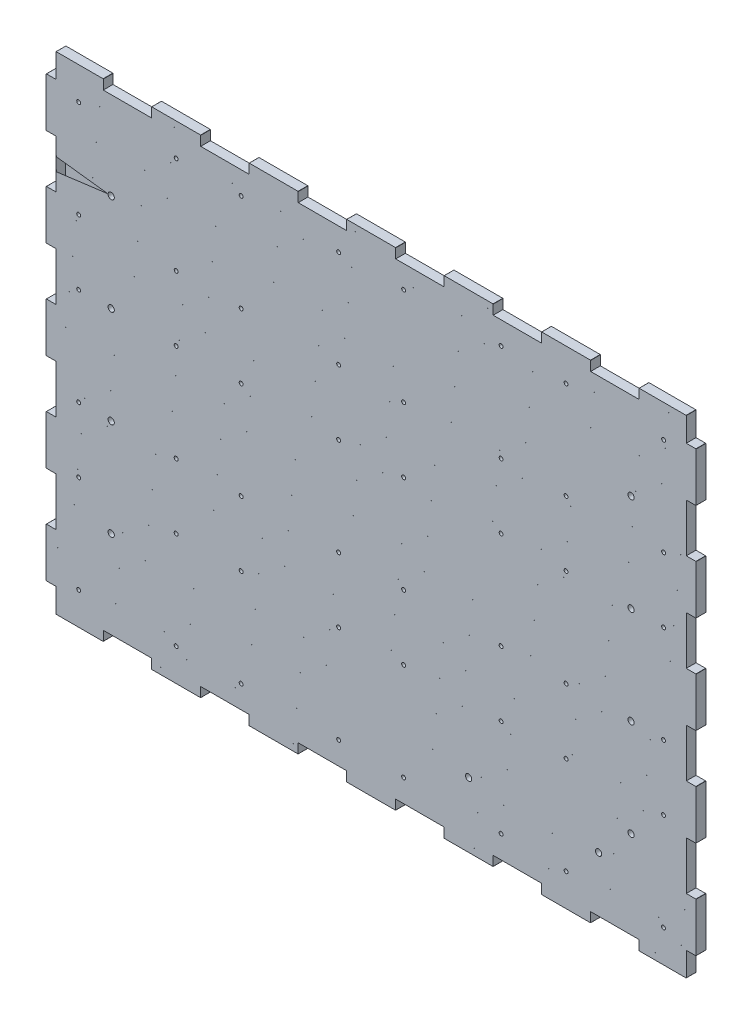
SolidWorks part; units mm, degrees
ref_plane "Front Plane" through (0, 0, 0) normal (0, 0, 1) x (1, 0, 0)
ref_plane "Top Plane" through (0, 0, 0) normal (0, 1, 0) x (1, 0, 0)
ref_plane "Right Plane" through (0, 0, 0) normal (1, 0, 0) x (0, 0, -1)
sketch "Model" plane through (0, 0, 0) normal (0, 0, 1) x (1, 0, 0)
  line L0 (-137.44, -124.95) -> (-137.43, -124.94)
  line L1 (-137.43, -124.94) -> (-137.42, -124.92)
  line L2 (-137.42, -124.92) -> (-137.41, -124.91)
  line L3 (-137.41, -124.91) -> (-137.4, -124.89)
  line L4 (-137.4, -124.89) -> (-137.4, -119.97)
  line L5 (-137.4, -119.97) -> (-112.6, -119.97)
  line L6 (-112.6, -119.97) -> (-112.6, -124.89)
  line L7 (-112.6, -124.89) -> (-112.58, -124.93)
  line L8 (-112.58, -124.93) -> (-112.57, -124.94)
  line L9 (-112.57, -124.94) -> (-112.55, -124.95)
  line L10 (-112.55, -124.95) -> (-112.54, -124.96)
  line L11 (-112.54, -124.96) -> (-112.52, -124.97)
  line L12 (-112.52, -124.97) -> (-87.48, -124.97)
  line L13 (-87.48, -124.97) -> (-87.44, -124.95)
  line L14 (-87.44, -124.95) -> (-87.43, -124.94)
  line L15 (-87.43, -124.94) -> (-87.42, -124.92)
  line L16 (-87.42, -124.92) -> (-87.41, -124.91)
  line L17 (-87.41, -124.91) -> (-87.4, -124.89)
  line L18 (-87.4, -124.89) -> (-87.4, -119.97)
  line L19 (-87.4, -119.97) -> (-62.6, -119.97)
  line L20 (-62.6, -119.97) -> (-62.6, -124.89)
  line L21 (-62.6, -124.89) -> (-62.58, -124.93)
  line L22 (-62.58, -124.93) -> (-62.57, -124.94)
  line L23 (-62.57, -124.94) -> (-62.55, -124.95)
  line L24 (-62.55, -124.95) -> (-62.54, -124.96)
  line L25 (-62.54, -124.96) -> (-62.52, -124.97)
  line L26 (-62.52, -124.97) -> (-37.48, -124.97)
  line L27 (-37.48, -124.97) -> (-37.44, -124.95)
  line L28 (-37.44, -124.95) -> (-37.43, -124.94)
  line L29 (-37.43, -124.94) -> (-37.42, -124.92)
  line L30 (-37.42, -124.92) -> (-37.41, -124.91)
  line L31 (-37.41, -124.91) -> (-37.4, -124.89)
  line L32 (-37.4, -124.89) -> (-37.4, -119.97)
  line L33 (-37.4, -119.97) -> (-12.6, -119.97)
  line L34 (-12.6, -119.97) -> (-12.6, -124.89)
  line L35 (-12.6, -124.89) -> (-12.58, -124.93)
  line L36 (-12.58, -124.93) -> (-12.57, -124.94)
  line L37 (-12.57, -124.94) -> (-12.55, -124.95)
  line L38 (-12.55, -124.95) -> (-12.54, -124.96)
  line L39 (-12.54, -124.96) -> (-12.52, -124.97)
  line L40 (-12.52, -124.97) -> (12.52, -124.97)
  line L41 (12.52, -124.97) -> (12.56, -124.95)
  line L42 (12.56, -124.95) -> (12.57, -124.94)
  line L43 (12.57, -124.94) -> (12.58, -124.92)
  line L44 (12.58, -124.92) -> (12.59, -124.91)
  line L45 (12.59, -124.91) -> (12.6, -124.89)
  line L46 (12.6, -124.89) -> (12.6, -119.97)
  line L47 (12.6, -119.97) -> (37.4, -119.97)
  line L48 (37.4, -119.97) -> (37.4, -124.89)
  line L49 (37.4, -124.89) -> (37.42, -124.93)
  line L50 (37.42, -124.93) -> (37.43, -124.94)
  line L51 (37.43, -124.94) -> (37.45, -124.95)
  line L52 (37.45, -124.95) -> (37.46, -124.96)
  line L53 (37.46, -124.96) -> (37.48, -124.97)
  line L54 (37.48, -124.97) -> (62.52, -124.97)
  line L55 (62.52, -124.97) -> (62.56, -124.95)
  line L56 (62.56, -124.95) -> (62.57, -124.94)
  line L57 (62.57, -124.94) -> (62.58, -124.92)
  line L58 (62.58, -124.92) -> (62.59, -124.91)
  line L59 (62.59, -124.91) -> (62.6, -124.89)
  line L60 (62.6, -124.89) -> (62.6, -119.97)
  line L61 (62.6, -119.97) -> (87.4, -119.97)
  line L62 (87.4, -119.97) -> (87.4, -124.89)
  line L63 (87.4, -124.89) -> (87.42, -124.93)
  line L64 (87.42, -124.93) -> (87.43, -124.94)
  line L65 (87.43, -124.94) -> (87.45, -124.95)
  line L66 (87.45, -124.95) -> (87.46, -124.96)
  line L67 (87.46, -124.96) -> (87.48, -124.97)
  line L68 (87.48, -124.97) -> (112.52, -124.97)
  line L69 (112.52, -124.97) -> (112.56, -124.95)
  line L70 (112.56, -124.95) -> (112.57, -124.94)
  line L71 (112.57, -124.94) -> (112.58, -124.92)
  line L72 (112.58, -124.92) -> (112.59, -124.91)
  line L73 (112.59, -124.91) -> (112.6, -124.89)
  line L74 (112.6, -124.89) -> (112.6, -119.97)
  line L75 (112.6, -119.97) -> (137.4, -119.97)
  line L76 (137.4, -119.97) -> (137.4, -124.89)
  line L77 (137.4, -124.89) -> (137.42, -124.93)
  line L78 (137.42, -124.93) -> (137.43, -124.94)
  line L79 (137.43, -124.94) -> (137.45, -124.95)
  line L80 (137.45, -124.95) -> (137.46, -124.96)
  line L81 (137.46, -124.96) -> (137.48, -124.97)
  line L82 (137.48, -124.97) -> (161.56, -124.97)
  line L83 (161.56, -124.97) -> (161.6, -124.95)
  line L84 (161.6, -124.95) -> (161.61, -124.94)
  line L85 (161.61, -124.94) -> (161.62, -124.92)
  line L86 (161.62, -124.92) -> (161.63, -124.91)
  line L87 (161.63, -124.91) -> (161.64, -124.89)
  line L88 (161.64, -124.89) -> (161.64, -112.6)
  line L89 (161.64, -112.6) -> (166.56, -112.6)
  line L90 (166.56, -112.6) -> (166.6, -112.58)
  line L91 (166.6, -112.58) -> (166.61, -112.57)
  line L92 (166.61, -112.57) -> (166.62, -112.55)
  line L93 (166.62, -112.55) -> (166.63, -112.54)
  line L94 (166.63, -112.54) -> (166.64, -112.52)
  line L95 (166.64, -112.52) -> (166.64, -87.48)
  line L96 (166.64, -87.48) -> (166.62, -87.44)
  line L97 (166.62, -87.44) -> (166.61, -87.43)
  line L98 (166.61, -87.43) -> (166.59, -87.42)
  line L99 (166.59, -87.42) -> (166.58, -87.41)
  line L100 (166.58, -87.41) -> (166.56, -87.4)
  line L101 (166.56, -87.4) -> (161.64, -87.4)
  line L102 (161.64, -87.4) -> (161.64, -62.6)
  line L103 (161.64, -62.6) -> (166.56, -62.6)
  line L104 (166.56, -62.6) -> (166.6, -62.58)
  line L105 (166.6, -62.58) -> (166.61, -62.57)
  line L106 (166.61, -62.57) -> (166.62, -62.55)
  line L107 (166.62, -62.55) -> (166.63, -62.54)
  line L108 (166.63, -62.54) -> (166.64, -62.52)
  line L109 (166.64, -62.52) -> (166.64, -37.48)
  line L110 (166.64, -37.48) -> (166.62, -37.44)
  line L111 (166.62, -37.44) -> (166.61, -37.43)
  line L112 (166.61, -37.43) -> (166.59, -37.42)
  line L113 (166.59, -37.42) -> (166.58, -37.41)
  line L114 (166.58, -37.41) -> (166.56, -37.4)
  line L115 (166.56, -37.4) -> (161.64, -37.4)
  line L116 (161.64, -37.4) -> (161.64, -12.6)
  line L117 (161.64, -12.6) -> (166.56, -12.6)
  line L118 (166.56, -12.6) -> (166.6, -12.58)
  line L119 (166.6, -12.58) -> (166.61, -12.57)
  line L120 (166.61, -12.57) -> (166.62, -12.55)
  line L121 (166.62, -12.55) -> (166.63, -12.54)
  line L122 (166.63, -12.54) -> (166.64, -12.52)
  line L123 (166.64, -12.52) -> (166.64, 12.52)
  line L124 (166.64, 12.52) -> (166.62, 12.56)
  line L125 (166.62, 12.56) -> (166.61, 12.57)
  line L126 (166.61, 12.57) -> (166.59, 12.58)
  line L127 (166.59, 12.58) -> (166.58, 12.59)
  line L128 (166.58, 12.59) -> (166.56, 12.6)
  line L129 (166.56, 12.6) -> (161.64, 12.6)
  line L130 (161.64, 12.6) -> (161.64, 37.4)
  line L131 (161.64, 37.4) -> (166.56, 37.4)
  line L132 (166.56, 37.4) -> (166.6, 37.42)
  line L133 (166.6, 37.42) -> (166.61, 37.43)
  line L134 (166.61, 37.43) -> (166.62, 37.45)
  line L135 (166.62, 37.45) -> (166.63, 37.46)
  line L136 (166.63, 37.46) -> (166.64, 37.48)
  line L137 (166.64, 37.48) -> (166.64, 62.52)
  line L138 (166.64, 62.52) -> (166.62, 62.56)
  line L139 (166.62, 62.56) -> (166.61, 62.57)
  line L140 (166.61, 62.57) -> (166.59, 62.58)
  line L141 (166.59, 62.58) -> (166.58, 62.59)
  line L142 (166.58, 62.59) -> (166.56, 62.6)
  line L143 (166.56, 62.6) -> (161.64, 62.6)
  line L144 (161.64, 62.6) -> (161.64, 87.4)
  line L145 (161.64, 87.4) -> (166.56, 87.4)
  line L146 (166.56, 87.4) -> (166.6, 87.42)
  line L147 (166.6, 87.42) -> (166.61, 87.43)
  line L148 (166.61, 87.43) -> (166.62, 87.45)
  line L149 (166.62, 87.45) -> (166.63, 87.46)
  line L150 (166.63, 87.46) -> (166.64, 87.48)
  line L151 (166.64, 87.48) -> (166.64, 112.52)
  line L152 (166.64, 112.52) -> (166.62, 112.56)
  line L153 (166.62, 112.56) -> (166.61, 112.57)
  line L154 (166.61, 112.57) -> (166.59, 112.58)
  line L155 (166.59, 112.58) -> (166.58, 112.59)
  line L156 (166.58, 112.59) -> (166.56, 112.6)
  line L157 (166.56, 112.6) -> (161.64, 112.6)
  line L158 (161.64, 112.6) -> (161.64, 124.89)
  line L159 (161.64, 124.89) -> (161.62, 124.93)
  line L160 (161.62, 124.93) -> (161.61, 124.94)
  line L161 (161.61, 124.94) -> (161.59, 124.95)
  line L162 (161.59, 124.95) -> (161.58, 124.96)
  line L163 (161.58, 124.96) -> (161.56, 124.97)
  line L164 (161.56, 124.97) -> (137.48, 124.97)
  line L165 (137.48, 124.97) -> (137.44, 124.95)
  line L166 (137.44, 124.95) -> (137.43, 124.94)
  line L167 (137.43, 124.94) -> (137.42, 124.92)
  line L168 (137.42, 124.92) -> (137.41, 124.91)
  line L169 (137.41, 124.91) -> (137.4, 124.89)
  line L170 (137.4, 124.89) -> (137.4, 119.97)
  line L171 (137.4, 119.97) -> (112.6, 119.97)
  line L172 (112.6, 119.97) -> (112.6, 124.89)
  line L173 (112.6, 124.89) -> (112.58, 124.93)
  line L174 (112.58, 124.93) -> (112.57, 124.94)
  line L175 (112.57, 124.94) -> (112.55, 124.95)
  line L176 (112.55, 124.95) -> (112.54, 124.96)
  line L177 (112.54, 124.96) -> (112.52, 124.97)
  line L178 (112.52, 124.97) -> (87.48, 124.97)
  line L179 (87.48, 124.97) -> (87.44, 124.95)
  line L180 (87.44, 124.95) -> (87.43, 124.94)
  line L181 (87.43, 124.94) -> (87.42, 124.92)
  line L182 (87.42, 124.92) -> (87.41, 124.91)
  line L183 (87.41, 124.91) -> (87.4, 124.89)
  line L184 (87.4, 124.89) -> (87.4, 119.97)
  line L185 (87.4, 119.97) -> (62.6, 119.97)
  line L186 (62.6, 119.97) -> (62.6, 124.89)
  line L187 (62.6, 124.89) -> (62.58, 124.93)
  line L188 (62.58, 124.93) -> (62.57, 124.94)
  line L189 (62.57, 124.94) -> (62.55, 124.95)
  line L190 (62.55, 124.95) -> (62.54, 124.96)
  line L191 (62.54, 124.96) -> (62.52, 124.97)
  line L192 (62.52, 124.97) -> (37.48, 124.97)
  line L193 (37.48, 124.97) -> (37.44, 124.95)
  line L194 (37.44, 124.95) -> (37.43, 124.94)
  line L195 (37.43, 124.94) -> (37.42, 124.92)
  line L196 (37.42, 124.92) -> (37.41, 124.91)
  line L197 (37.41, 124.91) -> (37.4, 124.89)
  line L198 (37.4, 124.89) -> (37.4, 119.97)
  line L199 (37.4, 119.97) -> (12.6, 119.97)
  line L200 (12.6, 119.97) -> (12.6, 124.89)
  line L201 (12.6, 124.89) -> (12.58, 124.93)
  line L202 (12.58, 124.93) -> (12.57, 124.94)
  line L203 (12.57, 124.94) -> (12.55, 124.95)
  line L204 (12.55, 124.95) -> (12.54, 124.96)
  line L205 (12.54, 124.96) -> (12.52, 124.97)
  line L206 (12.52, 124.97) -> (-12.52, 124.97)
  line L207 (-12.52, 124.97) -> (-12.56, 124.95)
  line L208 (-12.56, 124.95) -> (-12.57, 124.94)
  line L209 (-12.57, 124.94) -> (-12.58, 124.92)
  line L210 (-12.58, 124.92) -> (-12.59, 124.91)
  line L211 (-12.59, 124.91) -> (-12.6, 124.89)
  line L212 (-12.6, 124.89) -> (-12.6, 119.97)
  line L213 (-12.6, 119.97) -> (-37.4, 119.97)
  line L214 (-37.4, 119.97) -> (-37.4, 124.89)
  line L215 (-37.4, 124.89) -> (-37.42, 124.93)
  line L216 (-37.42, 124.93) -> (-37.43, 124.94)
  line L217 (-37.43, 124.94) -> (-37.45, 124.95)
  line L218 (-37.45, 124.95) -> (-37.46, 124.96)
  line L219 (-37.46, 124.96) -> (-37.48, 124.97)
  line L220 (-37.48, 124.97) -> (-62.52, 124.97)
  line L221 (-62.52, 124.97) -> (-62.56, 124.95)
  line L222 (-62.56, 124.95) -> (-62.57, 124.94)
  line L223 (-62.57, 124.94) -> (-62.58, 124.92)
  line L224 (-62.58, 124.92) -> (-62.59, 124.91)
  line L225 (-62.59, 124.91) -> (-62.6, 124.89)
  line L226 (-62.6, 124.89) -> (-62.6, 119.97)
  line L227 (-62.6, 119.97) -> (-87.4, 119.97)
  line L228 (-87.4, 119.97) -> (-87.4, 124.89)
  line L229 (-87.4, 124.89) -> (-87.42, 124.93)
  line L230 (-87.42, 124.93) -> (-87.43, 124.94)
  line L231 (-87.43, 124.94) -> (-87.45, 124.95)
  line L232 (-87.45, 124.95) -> (-87.46, 124.96)
  line L233 (-87.46, 124.96) -> (-87.48, 124.97)
  line L234 (-87.48, 124.97) -> (-112.52, 124.97)
  line L235 (-112.52, 124.97) -> (-112.56, 124.95)
  line L236 (-112.56, 124.95) -> (-112.57, 124.94)
  line L237 (-112.57, 124.94) -> (-112.58, 124.92)
  line L238 (-112.58, 124.92) -> (-112.59, 124.91)
  line L239 (-112.59, 124.91) -> (-112.6, 124.89)
  line L240 (-112.6, 124.89) -> (-112.6, 119.97)
  line L241 (-112.6, 119.97) -> (-137.4, 119.97)
  line L242 (-137.4, 119.97) -> (-137.4, 124.89)
  line L243 (-137.4, 124.89) -> (-137.42, 124.93)
  line L244 (-137.42, 124.93) -> (-137.43, 124.94)
  line L245 (-137.43, 124.94) -> (-137.45, 124.95)
  line L246 (-137.45, 124.95) -> (-137.46, 124.96)
  line L247 (-137.46, 124.96) -> (-137.48, 124.97)
  line L248 (-137.48, 124.97) -> (-161.56, 124.97)
  line L249 (-161.56, 124.97) -> (-161.6, 124.95)
  line L250 (-161.6, 124.95) -> (-161.61, 124.94)
  line L251 (-161.61, 124.94) -> (-161.62, 124.92)
  line L252 (-161.62, 124.92) -> (-161.63, 124.91)
  line L253 (-161.63, 124.91) -> (-161.64, 124.89)
  line L254 (-161.64, 124.89) -> (-161.64, 112.6)
  line L255 (-161.64, 112.6) -> (-166.56, 112.6)
  line L256 (-166.56, 112.6) -> (-166.6, 112.58)
  line L257 (-166.6, 112.58) -> (-166.61, 112.57)
  line L258 (-166.61, 112.57) -> (-166.62, 112.55)
  line L259 (-166.62, 112.55) -> (-166.63, 112.54)
  line L260 (-166.63, 112.54) -> (-166.64, 112.52)
  line L261 (-166.64, 112.52) -> (-166.64, 87.48)
  line L262 (-166.64, 87.48) -> (-166.62, 87.44)
  line L263 (-166.62, 87.44) -> (-166.61, 87.43)
  line L264 (-166.61, 87.43) -> (-166.59, 87.42)
  line L265 (-166.59, 87.42) -> (-166.58, 87.41)
  line L266 (-166.58, 87.41) -> (-166.56, 87.4)
  line L267 (-166.56, 87.4) -> (-161.64, 87.4)
  line L268 (-161.64, 87.4) -> (-161.64, 62.6)
  line L269 (-161.64, 62.6) -> (-166.56, 62.6)
  line L270 (-166.56, 62.6) -> (-166.6, 62.58)
  line L271 (-166.6, 62.58) -> (-166.61, 62.57)
  line L272 (-166.61, 62.57) -> (-166.62, 62.55)
  line L273 (-166.62, 62.55) -> (-166.63, 62.54)
  line L274 (-166.63, 62.54) -> (-166.64, 62.52)
  line L275 (-166.64, 62.52) -> (-166.64, 37.48)
  line L276 (-166.64, 37.48) -> (-166.62, 37.44)
  line L277 (-166.62, 37.44) -> (-166.61, 37.43)
  line L278 (-166.61, 37.43) -> (-166.59, 37.42)
  line L279 (-166.59, 37.42) -> (-166.58, 37.41)
  line L280 (-166.58, 37.41) -> (-166.56, 37.4)
  line L281 (-166.56, 37.4) -> (-161.64, 37.4)
  line L282 (-161.64, 37.4) -> (-161.64, 12.6)
  line L283 (-161.64, 12.6) -> (-166.56, 12.6)
  line L284 (-166.56, 12.6) -> (-166.6, 12.58)
  line L285 (-166.6, 12.58) -> (-166.61, 12.57)
  line L286 (-166.61, 12.57) -> (-166.62, 12.55)
  line L287 (-166.62, 12.55) -> (-166.63, 12.54)
  line L288 (-166.63, 12.54) -> (-166.64, 12.52)
  line L289 (-166.64, 12.52) -> (-166.64, -12.52)
  line L290 (-166.64, -12.52) -> (-166.62, -12.56)
  line L291 (-166.62, -12.56) -> (-166.61, -12.57)
  line L292 (-166.61, -12.57) -> (-166.59, -12.58)
  line L293 (-166.59, -12.58) -> (-166.58, -12.59)
  line L294 (-166.58, -12.59) -> (-166.56, -12.6)
  line L295 (-166.56, -12.6) -> (-161.64, -12.6)
  line L296 (-161.64, -12.6) -> (-161.64, -37.4)
  line L297 (-161.64, -37.4) -> (-166.56, -37.4)
  line L298 (-166.56, -37.4) -> (-166.6, -37.42)
  line L299 (-166.6, -37.42) -> (-166.61, -37.43)
  line L300 (-166.61, -37.43) -> (-166.62, -37.45)
  line L301 (-166.62, -37.45) -> (-166.63, -37.46)
  line L302 (-166.63, -37.46) -> (-166.64, -37.48)
  line L303 (-166.64, -37.48) -> (-166.64, -62.52)
  line L304 (-166.64, -62.52) -> (-166.62, -62.56)
  line L305 (-166.62, -62.56) -> (-166.61, -62.57)
  line L306 (-166.61, -62.57) -> (-166.59, -62.58)
  line L307 (-166.59, -62.58) -> (-166.58, -62.59)
  line L308 (-166.58, -62.59) -> (-166.56, -62.6)
  line L309 (-166.56, -62.6) -> (-161.64, -62.6)
  line L310 (-161.64, -62.6) -> (-161.64, -87.4)
  line L311 (-161.64, -87.4) -> (-166.56, -87.4)
  line L312 (-166.56, -87.4) -> (-166.6, -87.42)
  line L313 (-166.6, -87.42) -> (-166.61, -87.43)
  line L314 (-166.61, -87.43) -> (-166.62, -87.45)
  line L315 (-166.62, -87.45) -> (-166.63, -87.46)
  line L316 (-166.63, -87.46) -> (-166.64, -87.48)
  line L317 (-166.64, -87.48) -> (-166.64, -112.52)
  line L318 (-166.64, -112.52) -> (-166.62, -112.56)
  line L319 (-166.62, -112.56) -> (-166.61, -112.57)
  line L320 (-166.61, -112.57) -> (-166.59, -112.58)
  line L321 (-166.59, -112.58) -> (-166.58, -112.59)
  line L322 (-166.58, -112.59) -> (-166.56, -112.6)
  line L323 (-166.56, -112.6) -> (-161.64, -112.6)
  line L324 (-161.64, -112.6) -> (-161.64, -124.89)
  line L325 (-161.64, -124.89) -> (-161.62, -124.93)
  line L326 (-161.62, -124.93) -> (-161.61, -124.94)
  line L327 (-161.61, -124.94) -> (-161.59, -124.95)
  line L328 (-161.59, -124.95) -> (-161.58, -124.96)
  line L329 (-161.58, -124.96) -> (-161.56, -124.97)
  line L330 (-161.56, -124.97) -> (-137.48, -124.97)
  line L331 (-137.48, -124.97) -> (-137.44, -124.95)
extrude "Boss-Extrude1" add sketch "Model" along normal blind 5
sketch "Sketch2" plane through (0, 0, 5) normal (0, 0, 1) x (1, 0, 0)
  line L0 (-150, 108.3333) -> (-100, 108.3333) construction
  line L1 (-100, 108.3333) -> (-100, 58.3333) construction
  line L2 (-100, 58.3333) -> (-150, 58.3333) construction
  line L3 (-150, 58.3333) -> (-150, 108.3333) construction
  line L6 (16.6667, -25) -> (-16.6667, 25) construction
  circle A0 centre (-150, 108.3333) radius 1
  circle A1 centre (-100, 108.3333) radius 1
  circle A2 centre (-100, 58.3333) radius 1
  circle A3 centre (-150, 58.3333) radius 1
  circle A4 centre (-16.6667, 58.3333) radius 1
  circle A5 centre (-66.6667, 58.3333) radius 1
  circle A6 centre (-66.6667, 108.3333) radius 1
  circle A7 centre (-16.6667, 108.3333) radius 1
  circle A8 centre (66.6667, 58.3333) radius 1
  circle A9 centre (16.6667, 58.3333) radius 1
  circle A10 centre (16.6667, 108.3333) radius 1
  circle A11 centre (66.6667, 108.3333) radius 1
  circle A12 centre (150, 58.3333) radius 1
  circle A13 centre (100, 58.3333) radius 1
  circle A14 centre (100, 108.3333) radius 1
  circle A15 centre (150, 108.3333) radius 1
  circle A24 centre (-16.6667, -25) radius 1
  circle A25 centre (-66.6667, -25) radius 1
  circle A26 centre (-66.6667, 25) radius 1
  circle A27 centre (-16.6667, 25) radius 1
  circle A28 centre (66.6667, -25) radius 1
  circle A29 centre (16.6667, -25) radius 1
  circle A30 centre (16.6667, 25) radius 1
  circle A31 centre (66.6667, 25) radius 1
  circle A32 centre (150, -25) radius 1
  circle A33 centre (100, -25) radius 1
  circle A34 centre (100, 25) radius 1
  circle A35 centre (150, 25) radius 1
  circle A44 centre (-16.6667, -108.3333) radius 1
  circle A45 centre (-66.6667, -108.3333) radius 1
  circle A46 centre (-66.6667, -58.3333) radius 1
  circle A47 centre (-16.6667, -58.3333) radius 1
  circle A48 centre (66.6667, -108.3333) radius 1
  circle A49 centre (16.6667, -108.3333) radius 1
  circle A50 centre (16.6667, -58.3333) radius 1
  circle A51 centre (66.6667, -58.3333) radius 1
  circle A52 centre (150, -108.3333) radius 1
  circle A53 centre (100, -108.3333) radius 1
  circle A54 centre (100, -58.3333) radius 1
  circle A55 centre (150, -58.3333) radius 1
  circle A84 centre (-100, -25) radius 1
  circle A85 centre (-150, -25) radius 1
  circle A86 centre (-150, 25) radius 1
  circle A87 centre (-100, 25) radius 1
  circle A88 centre (-100, -108.3333) radius 1
  circle A89 centre (-150, -108.3333) radius 1
  circle A90 centre (-150, -58.3333) radius 1
  circle A91 centre (-100, -58.3333) radius 1
  dimension "D2" = 2
  dimension "D1" = 50
  dimension "D7" = 33.3333
  dimension "D8" = 33.3333
  dimension "D5" = 4
  dimension "D6" = 3
extrude "Cut-Extrude3" cut sketch "Sketch2" against normal through all
sketch "Sketch3" plane through (0, 0, 5) normal (0, 0, 1) x (1, 0, 0)
  line L0 (-2.5, 121.6667) -> (-2.5, 124.87) construction
  line L1 (-161.5, 121.6667) -> (-2.5, 121.6667)
  line L2 (-161.5, 121.6667) -> (-161.5, 111.6667) construction
  line L3 (-161.5, 111.6667) -> (161.5, 111.6667)
  line L4 (161.5, 121.6667) -> (161.5, 111.6667) construction
  line L5 (-161.5, 121.6667) -> (161.5, 111.6667) construction
  line L6 (-161.5, 111.6667) -> (161.5, 121.6667) construction
  line L7 (-2.5, 121.6667) -> (-2.5, 111.6667) construction
  line L8 (2.5, 121.6667) -> (2.5, 111.6667) construction
  line L9 (166.5367, 124.87) -> (-166.5367, 124.87) construction
  line L10 (-161.5, 105) -> (-161.5, 95) construction
  line L11 (-161.5, 105) -> (161.5, 105) construction
  line L12 (161.5, 105) -> (161.5, 95) construction
  line L13 (-161.5, 95) -> (161.5, 95) construction
  line L14 (-161.5, 88.3333) -> (-161.5, 78.3333) construction
  line L15 (-161.5, 88.3333) -> (161.5, 88.3333) construction
  line L16 (161.5, 88.3333) -> (161.5, 78.3333) construction
  line L17 (-161.5, 78.3333) -> (161.5, 78.3333) construction
  line L18 (-161.5, 71.6667) -> (-161.5, 61.6667) construction
  line L19 (-161.5, 71.6667) -> (161.5, 71.6667) construction
  line L20 (161.5, 71.6667) -> (161.5, 61.6667) construction
  line L21 (-161.5, 61.6667) -> (161.5, 61.6667) construction
  line L22 (-161.5, 55) -> (-161.5, 45) construction
  line L23 (-161.5, 55) -> (161.5, 55) construction
  line L24 (161.5, 55) -> (161.5, 45) construction
  line L25 (-161.5, 45) -> (161.5, 45) construction
  line L26 (-161.5, 38.3333) -> (-161.5, 28.3333) construction
  line L27 (-161.5, 38.3333) -> (161.5, 38.3333) construction
  line L28 (161.5, 38.3333) -> (161.5, 28.3333) construction
  line L29 (-161.5, 28.3333) -> (161.5, 28.3333) construction
  line L30 (-161.5, 21.6667) -> (-161.5, 11.6667) construction
  line L31 (-161.5, 21.6667) -> (161.5, 21.6667) construction
  line L32 (161.5, 21.6667) -> (161.5, 11.6667) construction
  line L33 (-161.5, 11.6667) -> (161.5, 11.6667) construction
  line L34 (-161.5, 5) -> (-161.5, -5) construction
  line L35 (-161.5, 5) -> (161.5, 5) construction
  line L36 (161.5, 5) -> (161.5, -5) construction
  line L37 (-161.5, -5) -> (161.5, -5) construction
  line L38 (-161.5, -11.6667) -> (-161.5, -21.6667) construction
  line L39 (-161.5, -11.6667) -> (161.5, -11.6667) construction
  line L40 (161.5, -11.6667) -> (161.5, -21.6667) construction
  line L41 (-161.5, -21.6667) -> (161.5, -21.6667) construction
  line L42 (-161.5, -28.3333) -> (-161.5, -38.3333) construction
  line L43 (-161.5, -28.3333) -> (161.5, -28.3333) construction
  line L44 (161.5, -28.3333) -> (161.5, -38.3333) construction
  line L45 (-161.5, -38.3333) -> (161.5, -38.3333) construction
  line L46 (-161.5, -45) -> (-161.5, -55) construction
  line L47 (-161.5, -45) -> (161.5, -45) construction
  line L48 (161.5, -45) -> (161.5, -55) construction
  line L49 (-161.5, -55) -> (161.5, -55) construction
  line L50 (-161.5, -61.6667) -> (-161.5, -71.6667) construction
  line L51 (-161.5, -61.6667) -> (161.5, -61.6667) construction
  line L52 (161.5, -61.6667) -> (161.5, -71.6667) construction
  line L53 (-161.5, -71.6667) -> (161.5, -71.6667) construction
  line L54 (-161.5, -78.3333) -> (-161.5, -88.3333) construction
  line L55 (-161.5, -78.3333) -> (161.5, -78.3333) construction
  line L56 (161.5, -78.3333) -> (161.5, -88.3333) construction
  line L57 (-161.5, -88.3333) -> (161.5, -88.3333) construction
  line L58 (-161.5, -95) -> (-161.5, -105) construction
  line L59 (-161.5, -95) -> (161.5, -95) construction
  line L60 (161.5, -95) -> (161.5, -105) construction
  line L61 (-161.5, -105) -> (161.5, -105) construction
  line L62 (-161.5, -111.6667) -> (-161.5, -121.6667) construction
  line L63 (-161.5, -111.6667) -> (161.5, -111.6667) construction
  line L64 (161.5, -111.6667) -> (161.5, -121.6667) construction
  line L65 (-161.5, -121.6667) -> (161.5, -121.6667) construction
  line L66 (166.5367, 124.87) -> (166.5367, -124.87) construction
  line L67 (0, 116.6667) -> (0, 111.6667) construction
  line L68 (0, 116.6667) -> (-2.5, 116.6667) construction
  line L69 (0, 116.6667) -> (2.5, 116.6667) construction
  line L70 (2.5, 121.6667) -> (161.5, 121.6667)
  line L71 (166.5367, -124.87) -> (-166.5367, -124.87) construction
  line L72 (-166.5367, 124.87) -> (-166.5367, -124.87) construction
  line L73 (166.5367, 124.87) -> (-166.5367, -124.87) construction
  line L74 (166.5367, -124.87) -> (-166.5367, 124.87) construction
  line L75 (0, -121.6667) -> (0, -124.87) construction
  point P4 (0, 116.6667)
  point P5 (-161.5, 0)
  point P10 (0, 0)
  point P71 (-161.5, 16.6667)
  point P75 (0, 0)
  dimension "D1" = 10
  dimension "D3" = 16.6667
  dimension "D4" = 5
  dimension "D5" = 333.0733
  dimension "D6" = 249.74
  dimension "D7" = 323
  dimension "D2" = 15
extrude "Cut-Extrude-Thin2" cut sketch "Sketch3" against normal blind 0.1 thin thin type mid plane wall 0.001
pattern_linear "LPattern1" count 15 spacing 16.6667 along (0, -1, 0) of "Cut-Extrude-Thin2"
sketch "Sketch4" plane through (0, 0, 5) normal (0, 0, 1) x (1, 0, 0)
  line L0 (-150, 58.3333) -> (-150, 108.3333) construction
  line L1 (-166.5367, 124.87) -> (166.5367, 124.87) construction
  line L2 (-166.5367, 124.87) -> (-166.5367, -124.87) construction
  line L3 (-166.5367, -124.87) -> (166.5367, -124.87) construction
  line L4 (166.5367, 124.87) -> (166.5367, -124.87) construction
  line L5 (-166.5367, 124.87) -> (166.5367, -124.87) construction
  line L6 (-166.5367, -124.87) -> (166.5367, 124.87) construction
  line L7 (-150, 108.3333) -> (-100, 108.3333) construction
  line L8 (0, -124.87) -> (0, 124.87) construction
  line L9 (166.5367, 0) -> (-166.5367, 0) construction
  line L10 (-161.64, 37.4) -> (-161.64, 12.6) construction
  circle A0 centre (-116.6667, 91.6667) radius 1.6
  circle A1 centre (-133.3333, 75) radius 1.6
  circle A2 centre (133.3333, 75) radius 1.6
  circle A3 centre (116.6667, 91.6667) radius 1.6
  circle A4 centre (133.3333, -75) radius 1.6
  circle A5 centre (116.6667, -91.6667) radius 1.6
  circle A6 centre (-116.6667, -91.6667) radius 1.6
  circle A7 centre (-133.3333, -75) radius 1.6
  circle A8 centre (-50, 91.6667) radius 1.6
  circle A9 centre (50, 91.6667) radius 1.6
  circle A10 centre (-66.6667, 108.3333) radius 1 construction
  circle A11 centre (50, -91.6667) radius 1.6
  circle A12 centre (-50, -91.6667) radius 1.6
  circle A13 centre (-133.3333, 25) radius 1.6
  circle A14 centre (-133.3333, -25) radius 1.6
  circle A16 centre (133.3333, 25) radius 1.6
  circle A17 centre (133.3333, -25) radius 1.6
  point P4 (0, 0)
  point P19 (0, 0)
  point P22 (0, 0)
  point P56 (-161.64, 25)
  dimension "D3" = 16.6667
  dimension "D6" = 3.2
  dimension "D1" = 333.0733
  dimension "D2" = 249.74
  dimension "D4" = 16.6667
  dimension "D5" = 16.6667
  dimension "D7" = 16.6667
  dimension "D8" = 16.6667
extrude "Cut-Extrude4" cut sketch "Sketch4" against normal through all
sketch "Sketch5" plane through (0, 0, 5) normal (0, 0, 1) x (1, 0, 0)
  line L0 (-137.4, -121.6662) -> (-137.4, -121.6672) construction
  line L1 (-137.4, -121.6662) -> (-137.4, -121.6672)
  line L2 (0, 0) -> (-166.64, 0) construction
  line L3 (-166.64, 12.52) -> (-166.64, -12.52) construction
  line L4 (-87.4, -121.6662) -> (-87.4, -121.6672)
  line L5 (-37.4, -121.6662) -> (-37.4, -121.6672)
  line L6 (12.6, -121.6662) -> (12.6, -121.6672)
  line L7 (62.6, -121.6662) -> (62.6, -121.6672)
  line L8 (112.6, -121.6662) -> (112.6, -121.6672)
  line L9 (112.6, -124.89) -> (112.6, -121.6672) construction
  line L10 (137.4, -121.6672) -> (137.4, -121.6662) construction
  line L11 (137.4, -121.6672) -> (137.4, -121.6662)
  line L12 (87.4, -121.6672) -> (87.4, -121.6662)
  line L13 (37.4, -121.6672) -> (37.4, -121.6662)
  line L14 (-12.6, -121.6672) -> (-12.6, -121.6662)
  line L15 (-62.6, -121.6672) -> (-62.6, -121.6662)
  line L16 (-112.6, -121.6672) -> (-112.6, -121.6662)
  line L17 (-112.6, -119.97) -> (-112.6, -121.6662) construction
  dimension "D1" = 6
  dimension "D2" = 6
extrude "Extrude-Thin2" add sketch "Sketch5" against normal up to surface (0.1 mm away) thin up to face at (-149.45, -121.6667, 4.9) thin type one direction wall 0.001
mirror "Mirror1" about plane through (0, 0, 0) normal (0, 1, 0) of "Extrude-Thin2"
equation "\"D5@Sketch3\"=(100/6)*20-0.26"
equation "\"D6@Sketch3\"=(100/6)*15-0.26"
equation "\"D3@LPattern1\"=100/6"
equation "\"D1@Sketch4\"=(100/6)*20-0.26"
equation "\"D2@Sketch4\"=(100/6)*15-0.26"
equation "\"D4@Sketch4\"=100/6"
equation "\"D5@Sketch4\"=100/6"
equation "\"D3@Sketch4\"=100/6"
equation "\"D7@Sketch4\"=100/6"
equation "\"D8@Sketch4\"=100/6"
